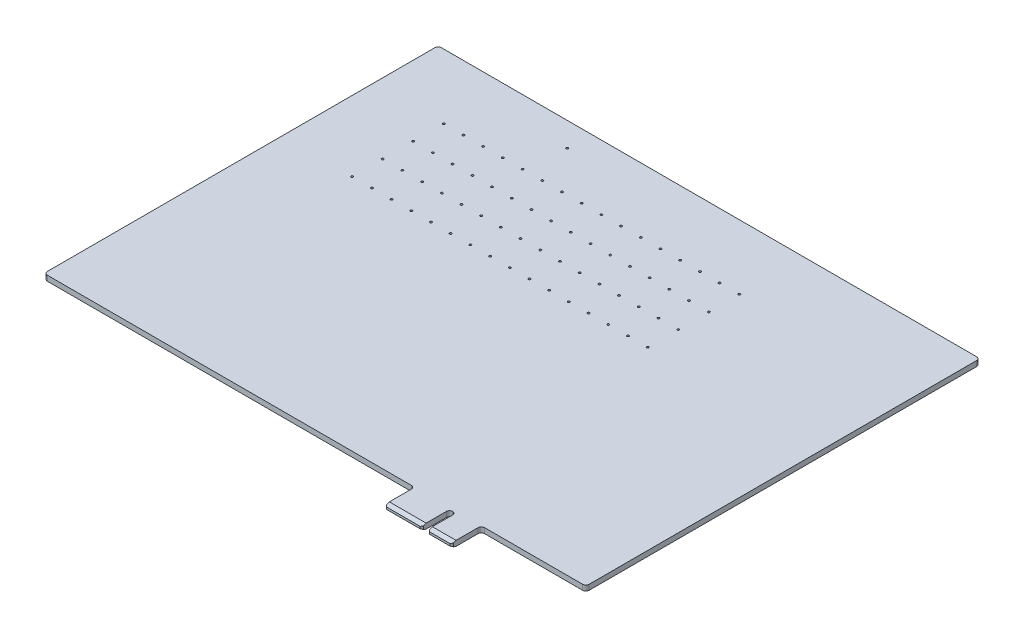
SolidWorks part; units mm, degrees
ref_plane "Front Plane" through (0, 0, 0) normal (0, 0, 1) x (1, 0, 0)
ref_plane "Top Plane" through (0, 0, 0) normal (0, 1, 0) x (1, 0, 0)
ref_plane "Right Plane" through (0, 0, 0) normal (1, 0, 0) x (0, 0, -1)
sketch "Sketch1" plane through (0, 0, 0) normal (0, 1, 0) x (1, 0, 0)
  line L1 (10, 10) -> (175, 10)
  line L2 (10, 10) -> (10, 139)
  line L3 (10, 139) -> (175, 139)
  line L4 (175, 10) -> (175, 139)
  dimension "D1" = 10
  dimension "D2" = 10
  dimension "D3" = 165
  dimension "D4" = 129
extrude "Boss-Extrude1" add sketch "Sketch1" along normal blind 1.6
sketch "Sketch2" plane through (0, 1.6, 0) normal (0, 1, 0) x (1, 0, 0)
  line L1 (10, 10) -> (122.85, 10)
  line L2 (10, 10) -> (10, 19)
  line L3 (10, 19) -> (122.85, 19)
  line L4 (122.85, 10) -> (122.85, 19)
  dimension "D1" = 9
  dimension "D2" = 112.85
extrude "Cut-Extrude1" cut sketch "Sketch2" against normal through all
sketch "Sketch3" plane through (0, 1.6, 0) normal (0, 1, 0) x (1, 0, 0)
  line L0 (122.85, 19) -> (10, 19) construction
  line L1 (175, 10) -> (143.15, 10)
  line L2 (175, 10) -> (175, 19)
  line L3 (175, 19) -> (143.15, 19)
  line L4 (143.15, 10) -> (143.15, 19)
  dimension "D1" = 31.85
extrude "Cut-Extrude2" cut sketch "Sketch3" against normal through all
sketch "Sketch4" plane through (0, 1.6, 0) normal (0, 1, 0) x (1, 0, 0)
  line L0 (122.85, 10) -> (143.15, 10) construction
  line L1 (134.05, 18.41) -> (135.95, 18.41)
  line L2 (134.05, 18.41) -> (134.05, 10)
  line L3 (134.05, 10) -> (135.95, 10)
  line L4 (135.95, 18.41) -> (135.95, 10)
  line L5 (134.05, 18.41) -> (135.95, 10) construction
  line L6 (134.05, 10) -> (135.95, 18.41) construction
  point P0 (135, 14.205)
  point P7 (135, 10)
  dimension "D1" = 8.41
  dimension "D2" = 1.9
  dimension "D3" = 135
extrude "Cut-Extrude3" cut sketch "Sketch4" against normal through all
fillet "Fillet1" radius 1 6 edges at (10, 0.8, -19) (10, 0.8, -139) (175, 0.8, -139) (175, 0.8, -19) (143.15, 0.8, -19) (122.85, 0.8, -19)
fillet "Fillet2" radius 0.95 2 edges at (135.95, 0.8, -18.41) (134.05, 0.8, -18.41)
chamfer "Chamfer1" distance 0.5 angle 45 4 edges at (143.15, 0.8, -10) (135.95, 0.8, -10) (134.05, 0.8, -10) (122.85, 0.8, -10)
hole_wizard "Ø0.65 (0.65) Diameter Hole1" positions "Sketch5" profile "Sketch6" hole size "Ø0.65" standard "DIN" end condition through all
sketch "Sketch5" plane through (0, 1.6, 0) normal (0, 1, 0) x (1, 0, 0)
  point P0 (31.402, 91.42)
  point P3 (0, 0)
  dimension "D1" = 31.402
  dimension "D2" = 91.42
sketch "Sketch6" plane through (31.402, 1.6, -91.42) normal (1, 0, 0) x (0, 0, 1)
  line L0 (0, 0) -> (0, 1.6)
  line L1 (0, 1.6) -> (0.325, 1.6)
  line L2 (0.325, 1.6) -> (0.325, 0)
  line L5 (0.325, 0) -> (0, 0)
  line L11 (0, -6.35) -> (0, 107.95) construction
  dimension "Thru Hole Dia." = 0.65
  dimension "Thru Hole Depth" = 1.6
pattern_linear "LPattern1" count 16 spacing 6 along (1, 0, 0) count 4 spacing 9.302 along (0, 0, -1) of "Ø0.65 (0.65) Diameter Hole1"
hole_wizard "Ø0.65 (0.65) Diameter Hole2" positions "Sketch9" profile "Sketch10" hole size "Ø0.65" standard "DIN" end condition through all
sketch "Sketch9" plane through (0, 1.6, 0) normal (0, 1, 0) x (1, 0, 0)
  point P0 (56.694, 131.618)
  dimension "D1" = 131.618
  dimension "D2" = 56.694
sketch "Sketch10" plane through (56.694, 1.6, -131.618) normal (1, 0, 0) x (0, 0, 1)
  line L0 (0, 0) -> (0, 1.6)
  line L1 (0, 1.6) -> (0.325, 1.6)
  line L2 (0.325, 1.6) -> (0.325, 0)
  line L5 (0.325, 0) -> (0, 0)
  line L11 (0, -6.35) -> (0, 107.95) construction
  dimension "Thru Hole Dia." = 0.65
  dimension "Thru Hole Depth" = 1.6
sketch "Sketch11" plane through (175, 0, 0) normal (1, 0, 0) x (0, 0, -1)
  line L0 (11.3, 1.6) -> (10, 1.1268)
  line L1 (18, 1.6) -> (10.5, 1.6) construction
  line L2 (10, 0) -> (10, 1.6) construction
  line L3 (10, 1.1268) -> (10, 1.6)
  line L4 (10, 1.6) -> (11.3, 1.6)
  line L5 (11.3, 0) -> (10, 0)
  line L6 (18, 0) -> (10.5, 0) construction
  line L7 (10, 0) -> (10, 0.4732)
  line L8 (10, 0.4732) -> (11.3, 0)
  dimension "D1" = 200
  dimension "D2" = 1.3
extrude "Cut-Extrude4" cut sketch "Sketch11" against normal through all
